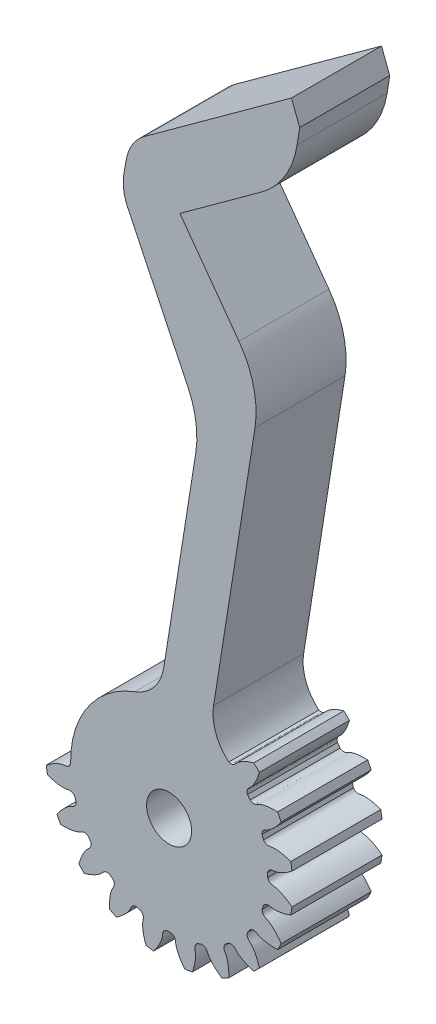
SolidWorks part; units mm, degrees
material "聚脂树脂"
ref_plane "前视基准面" through (0, 0, 0) normal (0, 0, 1) x (1, 0, 0)
ref_plane "上视基准面" through (0, 0, 0) normal (0, 1, 0) x (1, 0, 0)
ref_plane "右视基准面" through (0, 0, 0) normal (1, 0, 0) x (0, 0, -1)
other "Configuration Table"
sketch "草图1" plane through (0, 0, 0) normal (0, 0, 1) x (1, 0, 0)
  circle A0 centre (0, 0) radius 13.75
extrude "凸台-拉伸1" add sketch "草图1" along normal blind 10
ref_axis "基准轴1" through (0, 0, -1.5) along (0, 0, 1)
sketch "草图2" plane through (0, 0, 0) normal (0, 0, 1) x (1, 0, 0)
  line L0 (0, 0) -> (0, 13.75) construction
  circle A0 centre (0, 0) radius 13.75 construction
  arc A1 (0.2416, 10.9348) -> (-0.2416, 10.9348) centre (0, 0) ccw
  arc A2 (3.9764, 15.6228) -> (-3.9764, 15.6228) centre (0, 0) ccw
  spline S0 degree 3 poles (0.2416, 10.9348) (0.764, 11.1168) (0.6964, 11.4839) (0.7661, 11.8375) (0.7736, 11.8719) (0.7829, 11.9108) (0.7941, 11.954) (0.8075, 12.0015) (0.8231, 12.0532) (0.8413, 12.1091) (0.8621, 12.169) (0.8857, 12.2329) (0.9123, 12.3007) (0.9421, 12.3723) (0.9752, 12.4476) (1.0117, 12.5264) (1.0519, 12.6088) (1.0959, 12.6945) (1.1438, 12.7834) (1.1957, 12.8755) (1.2519, 12.9705) (1.3125, 13.0684) (1.3775, 13.1691) (1.4472, 13.2723) (1.5216, 13.3779) (1.601, 13.4858) (1.6853, 13.5958) (1.7747, 13.7078) (1.8694, 13.8216) (1.9693, 13.937) (2.0748, 14.0539) (2.1857, 14.1721) (2.3023, 14.2914) (2.4246, 14.4116) (2.5527, 14.5326) (2.6866, 14.6542) (2.8265, 14.7761) (2.9725, 14.8983) (3.1245, 15.0204) (3.2826, 15.1424) (3.4469, 15.2639) (3.6768, 15.427) (3.8549, 15.5454) (3.9764, 15.6228) knots 0 0 0 0 0.165916 0.170906 0.176664 0.183189 0.190482 0.198542 0.207371 0.216967 0.22733 0.238462 0.250361 0.263027 0.276462 0.290664 0.305634 0.321371 0.337876 0.355149 0.37319 0.391998 0.411574 0.431917 0.453028 0.474907 0.497554 0.520968 0.54515 0.570099 0.595817 0.622302 0.649554 0.677575 0.706363 0.735918 0.766242 0.797333 0.829191 0.861818 0.895212 0.929373 1 1 1 1
  spline S1 degree 3 poles (-0.2416, 10.9348) (-0.764, 11.1168) (-0.6964, 11.4839) (-0.7661, 11.8375) (-0.7736, 11.8719) (-0.7829, 11.9108) (-0.7941, 11.954) (-0.8075, 12.0015) (-0.8231, 12.0532) (-0.8413, 12.1091) (-0.8621, 12.169) (-0.8857, 12.2329) (-0.9123, 12.3007) (-0.9421, 12.3723) (-0.9752, 12.4476) (-1.0117, 12.5264) (-1.0519, 12.6088) (-1.0959, 12.6945) (-1.1438, 12.7834) (-1.1957, 12.8755) (-1.2519, 12.9705) (-1.3125, 13.0684) (-1.3775, 13.1691) (-1.4472, 13.2723) (-1.5216, 13.3779) (-1.601, 13.4858) (-1.6853, 13.5958) (-1.7747, 13.7078) (-1.8694, 13.8216) (-1.9693, 13.937) (-2.0748, 14.0539) (-2.1857, 14.1721) (-2.3023, 14.2914) (-2.4246, 14.4116) (-2.5527, 14.5326) (-2.6866, 14.6542) (-2.8265, 14.7761) (-2.9725, 14.8983) (-3.1245, 15.0204) (-3.2826, 15.1424) (-3.4469, 15.2639) (-3.6768, 15.427) (-3.8549, 15.5454) (-3.9764, 15.6228) knots 0 0 0 0 0.165916 0.170906 0.176664 0.183189 0.190482 0.198542 0.207371 0.216967 0.22733 0.238462 0.250361 0.263027 0.276462 0.290664 0.305634 0.321371 0.337876 0.355149 0.37319 0.391998 0.411574 0.431917 0.453028 0.474907 0.497554 0.520968 0.54515 0.570099 0.595817 0.622302 0.649554 0.677575 0.706363 0.735918 0.766242 0.797333 0.829191 0.861818 0.895212 0.929373 1 1 1 1
extrude "切除-拉伸1" cut sketch "草图2" along normal through all
pattern_circular "阵列(圆周)1" count 20 every 18 about axis through (0, 0, -1.5) along (0, 0, 1) of "切除-拉伸1"
sketch "草图6" plane through (0, 0, 0) normal (0, 0, -1) x (-1, 0, 0)
  line L0 (0, 0) -> (-10.311, 65.1009) construction
  line L1 (0, 0) -> (38.9643, 6.1713) construction
  line L2 (0, 0) -> (-30.4582, -4.8241) construction
  line L3 (-12.3461, -1.9554) -> (-21.1812, 53.827) construction
  line L4 (2.7655, 0.438) -> (-2.908, 36.2591)
  line L5 (-2.7655, -0.438) -> (-8.439, 35.383)
  line L6 (-8.439, 35.383) -> (-14.5014, 73.6592)
  line L7 (-14.5014, 73.6592) -> (-21.4537, 55.5478) construction
  line L8 (-14.5014, 73.6592) -> (-7.9754, 90.6601) construction
  line L9 (-14.5014, 73.6592) -> (-11.8644, 80.5287)
  line L10 (-2.7655, -0.438) -> (2.7655, 0.438)
  line L11 (-2.908, 36.2591) -> (-3.4495, 39.6781)
  line L12 (-1.2001, 58.7556) -> (-18.2459, 35.2942)
  line L13 (-18.2459, 35.2942) -> (-41.7074, 52.3399)
  line L14 (-41.7074, 52.3399) -> (-24.6616, 75.8014)
  line L15 (-24.6616, 75.8014) -> (-1.2001, 58.7556)
  line L16 (-13.5857, 76.0446) -> (4.2126, 63.1133)
  line L17 (-2.6302, 59.7947) -> (-0.6549, 60.1076)
  line L18 (-0.6549, 60.1076) -> (-0.2638, 57.6384)
  line L19 (-0.2638, 57.6384) -> (-2.2392, 57.3255)
  line L20 (-3.4495, 39.6781) -> (5.2176, 57.7026)
  circle A0 centre (0, 0) radius 12.5 construction
  circle A1 centre (-21.4537, 55.5478) radius 24 construction
  circle A2 centre (-21.4537, 55.5478) radius 26.7582 construction
  arc A3 (-11.8644, 80.5287) -> (-2.908, 36.2591) centre (-21.4537, 55.5478) cw
  arc A4 (-12.8529, 77.9537) -> (-8.439, 35.383) centre (-21.4537, 55.5478) cw
  circle A5 centre (-21.4537, 55.5478) radius 20.5061 construction
  dimension "D1" = 25
  dimension "D4" = 48
  dimension "D5" = 30
  dimension "D6" = 29
  dimension "D2" = 5.6
  dimension "D3" = 58.22
  dimension "D7" = 22
  dimension "D8" = 20
  dimension "D9" = 2
  dimension "D10" = 2
  dimension "D11" = 2.5
extrude "凸台-拉伸2" add sketch "草图6" against normal blind 10 contours L5 | L4 | A4 L16 L9 L6 L15 L12 | L11 A4 L5 L10 L4 | L16 A4 L20 A3 | L19 L18 L17 L15 L12 region at (2.9183, 18.697, 0) region at (6.0839, 37.6928, 0) region at (-3.1654, 59.6364, 0) region at (1.1851, 58.758, 0)
ref_plane "基准面1" through (12.5, 0, 0) normal (1, 0, 0) x (0, 0, -1)
ref_axis "基准轴2" through (0, 0, -6) along (0, 0, 1)
ref_plane "基准面2" through (0, 0, 0) normal (-0.9877, 0.1564, 0) x (0, 0, 1)
ref_plane "基准面3" through (12.3461, -1.9554, 0) normal (-0.9877, 0.1564, 0) x (0, 0, 1)
sketch "草图16" plane through (0, 0, 10) normal (0, 0, 1) x (1, 0, 0)
  circle A0 centre (0, 0) radius 2.5
  dimension "D1" = 5
extrude "切除-拉伸5" cut sketch "草图16" against normal blind 16.5
sketch "草图19" plane through (0, 0, 0) normal (0, 0, -1) x (-1, 0, 0)
  circle A0 centre (0, 0) radius 8
  dimension "D1" = 16
extrude "切除-拉伸7" cut sketch "草图19" against normal blind 3.4
sketch "草图20" plane through (0, 0, 0) normal (0, 0, -1) x (-1, 0, 0)
  line L0 (0, 0) -> (3.6089, 10.325)
  line L1 (3.6089, 10.325) -> (7.1451, 20.4421)
  line L2 (0, 0) -> (10.9348, -0.2416)
  line L3 (10.9348, -0.2416) -> (20.7519, -0.2416)
  circle A0 centre (0, 0) radius 17.5
  circle A1 centre (0, 0) radius 10.9375
  arc A2 (-8.7044, 6.6228) -> (-8.9885, 6.2318) centre (0, 0) ccw construction
  dimension "D1" = 35
extrude "切除-拉伸8" cut sketch "草图20" against normal blind 10 contours A1 L3 A0 L1 region at (-11.1082, 7.7459, 0)
sketch "草图23" plane through (0, 0, 10) normal (0, 0, 1) x (1, 0, 0)
  line L0 (-0.8941, 12.254) -> (-4.4195, -10.0048)
  line L1 (3.4495, 39.6781) -> (-0.8941, 12.254) construction
  line L2 (4.637, 11.3779) -> (1.1115, -10.8809)
  line L3 (10.1827, 46.3921) -> (4.637, 11.3779) construction
  circle A0 centre (0, 0) radius 10.9375
  arc A1 (-1.7221, 13.6417) -> (-2.5777, 13.5062) centre (0, 0) ccw construction
  arc A2 (-1.7221, 13.6417) -> (-2.5777, 13.5062) centre (0, 0) ccw
  arc A3 (6.6252, 12.0486) -> (5.8534, 12.4419) centre (0, 0) ccw construction
  arc A4 (6.6252, 12.0486) -> (5.8534, 12.4419) centre (0, 0) ccw
  spline S0 degree 3 poles (1994.3055, 137.7545) (-128.5866, -24.524) (-16.3079, 32.6766) (-1.5748, 13.4516) (-1.4488, 13.2768) (-1.314, 13.073) (-1.1971, 12.8801) (-1.0972, 12.6991) (-1.0129, 12.531) (-0.9532, 12.399) (3.5862, 1.4807) (-43.0829, -30.0698) (-1987.3608, -217.4346) knots -11.303808 -11.303808 -11.303808 -11.303808 0.502446 0.525093 0.568083 0.608002 0.644851 0.678629 0.709336 0.736973 0.749639 6.505013 6.505013 6.505013 6.505013 only from (-1.7221, 13.6417) to (-0.8941, 12.254) construction
  spline S1 degree 3 poles (-2000.7324, -84.7349) (23.8247, 5.3776) (-2.3586, 6.7359) (-2.931, 11.5081) (-2.9354, 11.558) (-2.9398, 11.6323) (-2.9424, 11.7223) (-2.941, 11.8445) (-2.9339, 11.9853) (-2.9194, 12.1444) (-2.8961, 12.3215) (-2.8626, 12.516) (-2.8175, 12.7274) (-2.7593, 12.9551) (-2.6999, 13.1539) (-2.6447, 13.3205) (5.4121, 36.1167) (129.8707, 16.4119) (-1939.2458, -485.2572) knots -2.172632 -2.172632 -2.172632 -2.172632 0.165916 0.170906 0.183189 0.190482 0.207371 0.22733 0.250361 0.276462 0.305634 0.337876 0.37319 0.411574 0.453028 0.474907 0.497554 12.30377 12.30377 12.30377 12.30377 only from (-3.1492, 10.4743) to (-2.5777, 13.5062) construction
  spline S2 degree 3 poles (-1.7221, 13.6417) (-1.653, 13.5549) (-1.5348, 13.399) (-1.3791, 13.1737) (-1.2534, 12.9751) (-1.1451, 12.788) (-1.0532, 12.6134) (-0.9763, 12.4522) (-0.9255, 12.3336) (-0.8999, 12.2691) (-0.8941, 12.254) knots 0.492568 0.492568 0.492568 0.492568 0.546972 0.588426 0.62681 0.662124 0.694366 0.723538 0.749639 0.75758 0.75758 0.75758 0.75758
  spline S3 degree 3 poles (-3.1492, 10.4743) (-2.7087, 10.8088) (-2.8864, 11.137) (-2.931, 11.5081) (-2.9354, 11.558) (-2.9398, 11.6323) (-2.9424, 11.7223) (-2.941, 11.8445) (-2.9339, 11.9853) (-2.9194, 12.1444) (-2.8961, 12.3215) (-2.8626, 12.516) (-2.8175, 12.7274) (-2.7593, 12.9551) (-2.6866, 13.1982) (-2.6232, 13.3832) (-2.5848, 13.4873) (-2.5777, 13.5062) knots 0 0 0 0 0.165916 0.170906 0.183189 0.190482 0.207371 0.22733 0.250361 0.276462 0.305634 0.337876 0.37319 0.411574 0.453028 0.497554 0.507432 0.507432 0.507432 0.507432
  spline S4 degree 3 poles (1694.4124, -1060.787) (-118.4443, 55.7411) (6.0134, 36.0216) (6.6326, 11.8082) (6.6318, 11.5928) (6.6211, 11.3487) (6.6022, 11.1239) (6.5767, 10.9187) (6.5461, 10.7332) (6.5119, 10.5675) (6.4757, 10.4216) (6.4439, 10.3125) (6.4137, 10.2194) (6.3905, 10.1545) (6.3633, 10.0853) (6.3437, 10.0391) (4.3246, 5.6774) (-20.9966, 12.4766) (1876.592, -698.8356) knots -11.303841 -11.303841 -11.303841 -11.303841 0.502446 0.525093 0.568083 0.608002 0.644851 0.678629 0.709336 0.736973 0.761538 0.783033 0.792629 0.809518 0.816811 0.829094 0.834084 3.172618 3.172618 3.172618 3.172618 only from (6.6252, 12.0486) to (6.2318, 8.9885) construction
  spline S5 degree 3 poles (1822.9113, -820.9251) (31.6823, -41.9116) (-2.9532, 2.5164) (4.7381, 11.4976) (4.8357, 11.6047) (4.9677, 11.7385) (5.1187, 11.8798) (5.2895, 12.0271) (5.4807, 12.1793) (5.6544, 12.3066) (25.6074, 26.0379) (114.7149, -63.0592) (-1854.132, 747.2879) knots -5.505024 -5.505024 -5.505024 -5.505024 0.250361 0.263027 0.290664 0.321371 0.355149 0.391998 0.431917 0.474907 0.497554 12.303815 12.303815 12.303815 12.303815 only from (4.637, 11.3779) to (5.8534, 12.4419) construction
  spline S6 degree 3 poles (6.6252, 12.0486) (6.6301, 11.9377) (6.6341, 11.7422) (6.6276, 11.4683) (6.6126, 11.2338) (6.5902, 11.0188) (6.5619, 10.8235) (6.5293, 10.6479) (6.4939, 10.4921) (6.4623, 10.3749) (6.4317, 10.2737) (6.4078, 10.2024) (6.3839, 10.1378) (6.3633, 10.0853) (6.3437, 10.0391) (6.1867, 9.7) (5.9162, 9.4428) (6.2318, 8.9885) knots 0.492568 0.492568 0.492568 0.492568 0.546972 0.588426 0.62681 0.662124 0.694366 0.723538 0.749639 0.77267 0.783033 0.801458 0.809518 0.816811 0.829094 0.834084 1 1 1 1
  spline S7 degree 3 poles (4.637, 11.3779) (4.6636, 11.4105) (4.7272, 11.4856) (4.8357, 11.6047) (4.9677, 11.7385) (5.1187, 11.8798) (5.2895, 12.0271) (5.4807, 12.1793) (5.6707, 12.3185) (5.798, 12.4053) (5.8534, 12.4419) knots 0.24242 0.24242 0.24242 0.24242 0.263027 0.290664 0.321371 0.355149 0.391998 0.431917 0.474907 0.507432 0.507432 0.507432 0.507432
extrude "切除-拉伸10" cut sketch "草图23" against normal blind 10 contours S3 A0 L0 S2 A2 | S7 L2 A0 S6 A4 region at (-1.9905, 12.0516, 10) region at (5.6172, 10.8467, 10)
fillet "圆角7" radius 5 2 edges at (4.4195, 10.0048, 5) (-1.1115, 10.8809, 5)
fillet "圆角11" radius 10 2 edges at (10.1827, 46.3921, 5) (13.5636, 67.7383, 5)
fillet "圆角12" radius 5 2 edges at (-5.2176, 57.7026, 5) (-4.2126, 63.1133, 5)
fillet "圆角13" radius 10 1 edges at (3.4495, 39.6781, 5)
